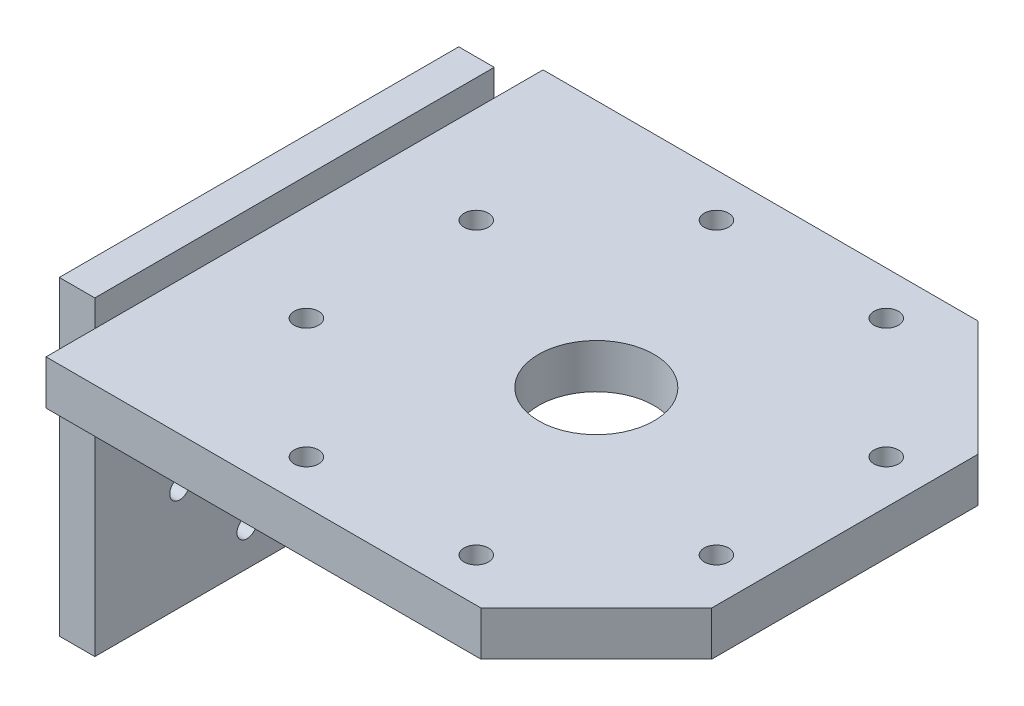
SolidWorks part; units mm, degrees
ref_plane "Front Plane" through (0, 0, 0) normal (0, 0, 1) x (1, 0, 0)
ref_plane "Top Plane" through (0, 0, 0) normal (0, 1, 0) x (1, 0, 0)
ref_plane "Right Plane" through (0, 0, 0) normal (1, 0, 0) x (0, 0, -1)
ref_plane "PL_Back_Plate_base" through (-76, 0, 0) normal (1, 0, 0) x (0, 0, -1)
sketch "SK_Back_Plate" plane through (-76, 0, 0) normal (1, 0, 0) x (0, 0, -1)
  line L0 (45, 36) -> (45, -34)
  line L1 (45, -34) -> (-45, -34)
  line L2 (-45, -34) -> (-45, 36)
  line L3 (-45, 36) -> (45, 36)
  circle A0 centre (25.8686, -10.7151) radius 2.25
  circle A1 centre (10.7151, -25.8686) radius 2.25
  circle A2 centre (-10.7151, -25.8686) radius 2.25
  circle A3 centre (-25.8686, -10.7151) radius 2.25
  circle A4 centre (-25.8686, 10.7151) radius 2.25
  circle A5 centre (-10.7151, 25.8686) radius 2.25
  circle A6 centre (10.7151, 25.8686) radius 2.25
  circle A7 centre (25.8686, 10.7151) radius 2.25
  circle A8 centre (0, 0) radius 6
  dimension "D9_SK_Back_Plate" = 4.5
  dimension "D12_SK_Back_Plate" = 4.5
  dimension "D15_SK_Back_Plate" = 4.5
  dimension "D18_SK_Back_Plate" = 4.5
  dimension "D21_SK_Back_Plate" = 4.5
  dimension "D24_SK_Back_Plate" = 4.5
  dimension "D27_SK_Back_Plate" = 4.5
  dimension "D30_SK_Back_Plate" = 4.5
  dimension "D33_SK_Back_Plate" = 12
  dimension "P1" = 45
  dimension "P2" = 36
  dimension "P3" = 45
  dimension "P4" = 34
  dimension "P5" = 45
  dimension "P6" = 34
  dimension "P7" = 45
  dimension "P8" = 36
  dimension "P10" = 25.8686
  dimension "P11" = 10.7151
  dimension "P13" = 10.7151
  dimension "P14" = 25.8686
  dimension "P16" = 10.7151
  dimension "P17" = 25.8686
  dimension "P19" = 25.8686
  dimension "P20" = 10.7151
  dimension "P22" = 25.8686
  dimension "P23" = 10.7151
  dimension "P25" = 10.7151
  dimension "P26" = 25.8686
  dimension "P28" = 10.7151
  dimension "P29" = 25.8686
  dimension "P31" = 25.8686
  dimension "P32" = 10.7151
extrude "Back_Plate" add sketch "SK_Back_Plate" along normal blind 8
ref_plane "PL_Roll_Pilot_Recess_base" through (-76, 0, 0) normal (1, 0, 0) x (0, 0, -1)
sketch "SK_Roll_Pilot_Recess" plane through (-76, 0, 0) normal (1, 0, 0) x (0, 0, -1)
  circle A0 centre (0, 0) radius 22.15
  dimension "D1_SK_Roll_Pilot_Recess" = 44.3
extrude "Roll_Pilot_Recess" cut sketch "SK_Roll_Pilot_Recess" along normal blind 2.2
ref_plane "PL_Medial_Plate_base" through (0, 20, 0) normal (0, 1, 0) x (1, 0, 0)
sketch "SK_Medial_Plate" plane through (0, 20, 0) normal (0, 1, 0) x (1, 0, 0)
  line L0 (-68, 56) -> (30, 56)
  line L1 (30, 56) -> (56, 30)
  line L2 (56, 30) -> (56, -30)
  line L3 (56, -30) -> (30, -56)
  line L4 (30, -56) -> (-68, -56)
  line L5 (-68, -56) -> (-68, 56)
  circle A0 centre (46.194, 19.1342) radius 2.75
  circle A1 centre (19.1342, 46.194) radius 2.75
  circle A2 centre (-19.1342, 46.194) radius 2.75
  circle A3 centre (-46.194, 19.1342) radius 2.75
  circle A4 centre (-46.194, -19.1342) radius 2.75
  circle A5 centre (-19.1342, -46.194) radius 2.75
  circle A6 centre (19.1342, -46.194) radius 2.75
  circle A7 centre (46.194, -19.1342) radius 2.75
  circle A8 centre (0, 0) radius 13
  dimension "D13_SK_Medial_Plate" = 5.5
  dimension "D16_SK_Medial_Plate" = 5.5
  dimension "D19_SK_Medial_Plate" = 5.5
  dimension "D22_SK_Medial_Plate" = 5.5
  dimension "D25_SK_Medial_Plate" = 5.5
  dimension "D28_SK_Medial_Plate" = 5.5
  dimension "D31_SK_Medial_Plate" = 5.5
  dimension "D34_SK_Medial_Plate" = 5.5
  dimension "D37_SK_Medial_Plate" = 26
  dimension "P1" = 68
  dimension "P2" = 56
  dimension "P3" = 30
  dimension "P4" = 56
  dimension "P5" = 56
  dimension "P6" = 30
  dimension "P7" = 56
  dimension "P8" = 30
  dimension "P9" = 30
  dimension "P10" = 56
  dimension "P11" = 68
  dimension "P12" = 56
  dimension "P14" = 46.194
  dimension "P15" = 19.1342
  dimension "P17" = 19.1342
  dimension "P18" = 46.194
  dimension "P20" = 19.1342
  dimension "P21" = 46.194
  dimension "P23" = 46.194
  dimension "P24" = 19.1342
  dimension "P26" = 46.194
  dimension "P27" = 19.1342
  dimension "P29" = 19.1342
  dimension "P30" = 46.194
  dimension "P32" = 19.1342
  dimension "P33" = 46.194
  dimension "P35" = 46.194
  dimension "P36" = 19.1342
extrude "Medial_Plate" add sketch "SK_Medial_Plate" along normal blind 10
equation "\"Roll_face_x\" = -76"
equation "\"Pitch_rear_y\" = -20"
equation "\"Plate_t\" = 10"
